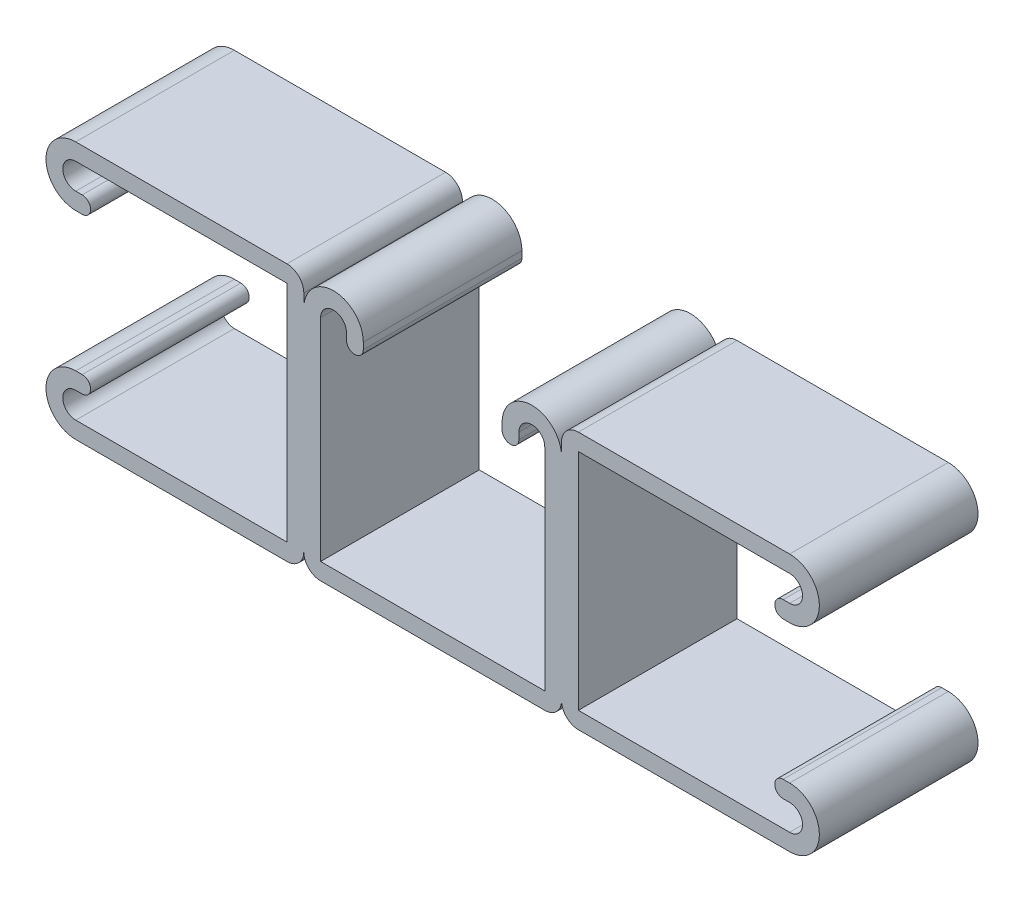
SolidWorks part; units mm, degrees
note: '?' marks a value the reader was unsure of.
ref_plane "Plane1" through (0, 0, 0) normal (0, 0, 1) x (1, 0, 0)
ref_plane "Plane2" through (0, 0, 0) normal (0, 1, 0) x (1, 0, 0)
ref_plane "Plane3" through (0, 0, 0) normal (1, 0, 0) x (0, 0, -1)
sketch "Sketch1" plane through (0, 0, 0) normal (0, 0, 1) x (1, 0, 0)
  line L0 (0, 36.5125) -> (0, 2.6924)
  line L1 (2.6924, 0) -> (38.5826, 0)
  line L2 (41.275, 2.6924) -> (41.275, 36.5125)
  line L3 (31.75, 36.5125) -> (31.75, 35.4774)
  line L4 (9.525, 36.5125) -> (9.525, 35.4774)
  line L5 (6.8326, 36.5125) -> (6.8326, 35.4774)
  line L6 (2.6924, 36.5125) -> (2.6924, 2.6924)
  line L7 (2.6924, 2.6924) -> (38.5826, 2.6924)
  line L8 (38.5826, 2.6924) -> (38.5826, 36.5125)
  line L9 (34.4424, 36.5125) -> (34.4424, 35.4774)
  line L10 (-4.7625, 41.275) -> (46.0375, 41.275) construction
  line L11 (7.7851, 34.1313) -> (33.4899, 34.1313) construction
  arc A0 (41.275, 36.5125) -> (31.75, 36.5125) centre (36.5125, 36.5125) ccw
  arc A1 (0, 36.5125) -> (9.525, 36.5125) centre (4.7625, 36.5125) cw
  arc A2 (2.6924, 0) -> (0, 2.6924) centre (2.6924, 2.6924) cw
  arc A3 (38.5826, 0) -> (41.275, 2.6924) centre (38.5826, 2.6924) ccw
  arc A4 (2.6924, 36.5125) -> (6.8326, 36.5125) centre (4.7625, 36.5125) cw
  arc A5 (38.5826, 36.5125) -> (34.4424, 36.5125) centre (36.5125, 36.5125) ccw
  arc A6 (31.75, 35.4774) -> (34.4424, 35.4774) centre (33.0962, 35.4774) ccw
  arc A7 (9.525, 35.4774) -> (6.8326, 35.4774) centre (8.1788, 35.4774) cw
  dimension "D6" = 9.525
  dimension "D7" = 22.225
  dimension "D9" = 7.1437
  dimension "D2" = 41.275
extrude "Base-Extrude" add sketch "Sketch1" along normal mid plane 25.4
ref_axis "Axis1" through (0, 0, -50) along (0, 0, 1)?
pattern_circular "CirPattern1" count 2 every 90 about axis through (0, 0, 0) along (0, 0, 1) of "Base-Extrude"
ref_plane "Plane5" through (41.275, 0, 0) normal (1, 0, 0) x (0, 0, -1)
ref_axis "Axis3" through (41.275, 0, 50) along (0, 0, -1)?
pattern_circular "CirPattern2" count 2 every 90 about axis through (41.275, 0, 0) along (0, 0, 1) of "Base-Extrude"
equation "\"D7@Sketch1\" = \"Width@Sketch1\" - 2 * \"D6@Sketch1\""
equation "\"D1@Sketch1\" = \"gauge@Sketch1\""
